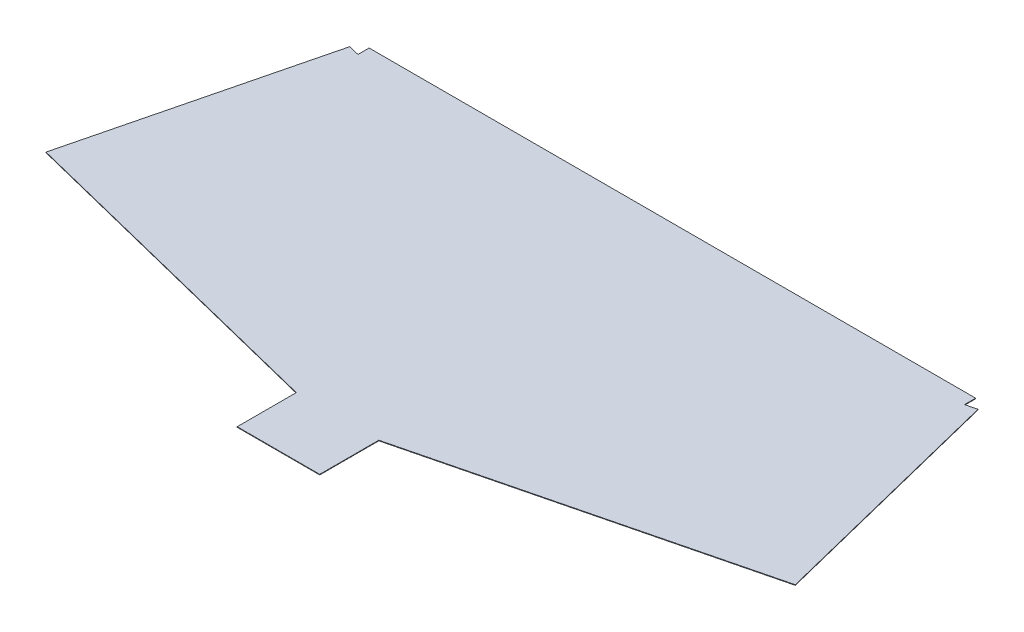
SolidWorks part; units mm, degrees
ref_plane "Front Plane" through (0, 0, 0) normal (0, 0, 1) x (1, 0, 0)
ref_plane "Top Plane" through (0, 0, 0) normal (0, 1, 0) x (1, 0, 0)
ref_plane "Right Plane" through (0, 0, 0) normal (1, 0, 0) x (0, 0, -1)
sketch "Sketch1" plane through (0, 0, 0) normal (0, 1, 0) x (1, 0, 0)
  line L0 (-432.3097, -519.7331) -> (-1010.9992, -375.4836)
  line L1 (-902.3097, 60.9164) -> (185.6903, 60.9164)
  line L2 (-902.3097, 60.9164) -> (-432.3097, -519.7331)
  line L3 (-432.3097, -519.7331) -> (-284.3097, -519.7331)
  line L4 (185.6903, 60.9164) -> (-284.3097, -519.7331)
  line L5 (-902.3097, 60.9164) -> (185.6903, 60.9164)
  line L6 (-902.3097, 60.9164) -> (-902.3097, 80.9164)
  line L7 (-902.3097, 80.9164) -> (185.6903, 80.9164)
  line L8 (185.6903, 60.9164) -> (185.6903, 80.9164)
  line L9 (-432.3097, -519.7331) -> (-284.3097, -519.7331)
  line L10 (-432.3097, -519.7331) -> (-432.3097, -625.7331)
  line L11 (-432.3097, -625.7331) -> (-284.3097, -625.7331)
  line L12 (-284.3097, -519.7331) -> (-284.3097, -625.7331)
  line L13 (-1010.9992, -375.4836) -> (-902.3097, 60.9164)
  line L14 (-284.3097, -519.7331) -> (294.3797, -375.4836)
  line L15 (294.3797, -375.4836) -> (185.6903, 60.9164)
  line L16 (-902.3097, 60.9164) -> (-1010.9992, -375.4836)
  line L17 (-902.3097, 60.9164) -> (-921.7169, 65.7499)
  line L18 (-1010.9992, -375.4836) -> (-1030.4063, -370.65)
  line L19 (-921.7169, 65.7499) -> (-1030.4063, -370.65)
  line L20 (294.3797, -375.4836) -> (185.6903, 60.9164)
  line L21 (294.3797, -375.4836) -> (313.7868, -370.65)
  line L22 (185.6903, 60.9164) -> (205.0974, 65.7499)
  line L23 (313.7868, -370.65) -> (205.0974, 65.7499)
  dimension "D1" = 1088
  dimension "D2" = 148
  dimension "D3" = 747.03
  dimension "D4" = 747.03
  dimension "D5" = 580.6495
  dimension "D6" = 20
  dimension "D7" = 106
  dimension "D8" = 596.397
  dimension "D9" = 449.7314
  dimension "D10" = 596.397
  dimension "D11" = 449.7314
  dimension "D12" = 20
  dimension "D13" = 20
extrude "Boss-Extrude1" add sketch "Sketch1" along normal blind 1 contours L14 L15 L4 | L12 L3 L10 L11 | L21 L23 L22 L15 | L1 L8 L7 L6 | L17 L19 L18 L13 | L13 L0 L2 | L4 L1 L2 L3 region at (-781.8729, 0, 278.1001) region at (-358.3097, 0, 155.8093) region at (-358.3097, 0, 572.7331) region at (-966.358, 0, 154.8668) region at (-358.3097, 0, -70.9164) region at (65.2534, 0, 278.1001) region at (249.7385, 0, 154.8668)
sketch "Sketch2" plane through (0, 1, 0) normal (0, 1, 0) x (1, 0, 0)
  line L0 (-902.3097, 60.9164) -> (185.6903, 60.9164) construction
  line L1 (185.6903, 60.9164) -> (294.3797, -375.4836) construction
  line L2 (-902.3097, 60.9164) -> (-1010.9992, -375.4836) construction
  line L3 (-902.3097, 60.9164) -> (-432.3097, -519.7331) construction
  line L4 (-284.3097, -519.7331) -> (185.6903, 60.9164) construction
  line L5 (-432.3097, -519.7331) -> (-284.3097, -519.7331) construction
